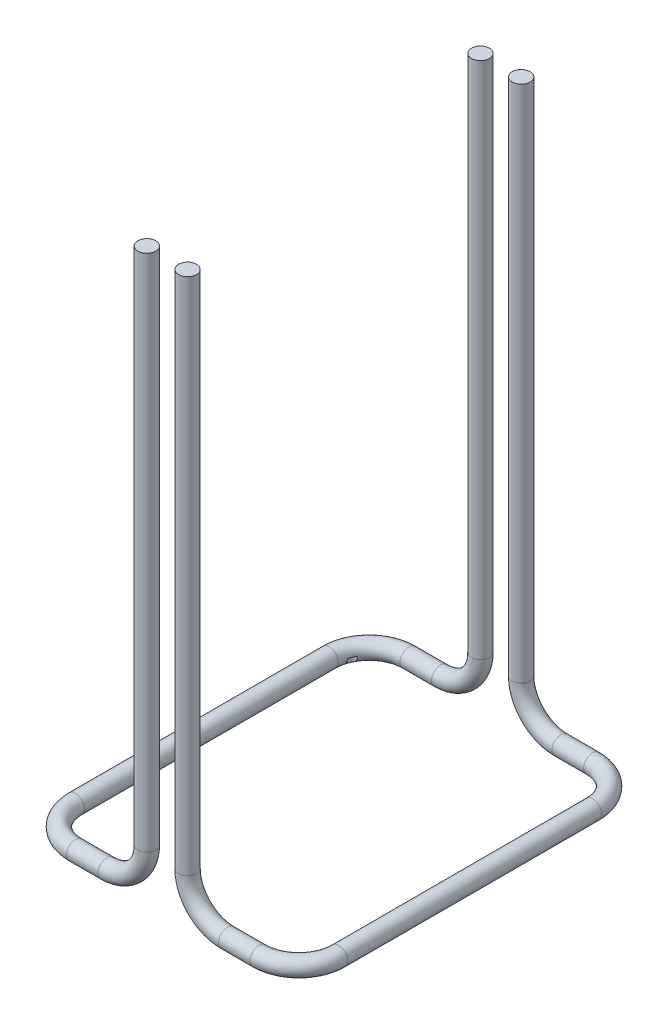
SolidWorks part; units mm, degrees
ref_plane "前视基准面" through (0, 0, 0) normal (0, 0, 1) x (1, 0, 0)
ref_plane "上视基准面" through (0, 0, 0) normal (0, 1, 0) x (1, 0, 0)
ref_plane "右视基准面" through (0, 0, 0) normal (1, 0, 0) x (0, 0, -1)
sketch3d "3D草图1"
  line L0 (0, 0, 0) -> (0, 51.939, 0) construction
  line L1 (25.5, 700.4535, 0) -> (25.5, 50.4535, 0)
  line L2 (75.5, 0.4535, 0) -> (114.9994, 0.4535, 0)
  line L3 (164.9994, 0.4535, -50) -> (164.9994, 0.4535, -368)
  line L4 (114.9994, 0.4535, -418) -> (75.5, 0.4535, -418)
  line L5 (25.5, 50.4535, -418) -> (25.5, 700.4535, -418)
  line L6 (-25.5, 50.4535, -418) -> (-25.5, 700.4535, -418)
  line L7 (-114.9994, 0.4535, -418) -> (-75.5, 0.4535, -418)
  line L8 (-164.9994, 0.4535, -50) -> (-164.9994, 0.4535, -368)
  line L9 (-75.5, 0.4535, 0) -> (-114.9994, 0.4535, 0)
  line L10 (-25.5, 700.4535, 0) -> (-25.5, 50.4535, 0)
  arc A0 (75.5, 0.4535, -418) -> (25.5, 50.4535, -418) centre (75.5, 50.4535, -418) ccw
  arc A1 (164.9994, 0.4535, -368) -> (114.9994, 0.4535, -418) centre (114.9994, 0.4535, -368) ccw
  arc A2 (114.9994, 0.4535, 0) -> (164.9994, 0.4535, -50) centre (114.9994, 0.4535, -50) ccw
  arc A3 (25.5, 50.4535, 0) -> (75.5, 0.4535, 0) centre (75.5, 50.4535, 0) ccw
  arc A4 (-75.5, 0.4535, 0) -> (-25.5, 50.4535, 0) centre (-75.5, 50.4535, 0) cw
  arc A5 (-164.9994, 0.4535, -50) -> (-114.9994, 0.4535, 0) centre (-114.9994, 0.4535, -50) cw
  arc A6 (-114.9994, 0.4535, -418) -> (-164.9994, 0.4535, -368) centre (-114.9994, 0.4535, -368) cw
  arc A7 (-25.5, 50.4535, -418) -> (-75.5, 0.4535, -418) centre (-75.5, 50.4535, -418) cw
  point P11 (25.5, 0.4535, -418)
  point P12 (75.5, 50.4535, -468)
  point P15 (164.9994, 0.4535, -418)
  point P16 (114.9994, 50.4535, -368)
  point P19 (164.9994, 0.4535, 0)
  point P20 (114.9994, 50.4535, -50)
  point P23 (25.5, 0.4535, 0)
  point P24 (75.5, 50.4535, 50)
  point P28 (-75.5, 50.4535, 50)
  point P32 (-114.9994, 50.4535, -50)
  point P36 (-114.9994, 50.4535, -368)
  point P40 (-75.5, 50.4535, -468)
  point P43 (-25.5, 0.4535, 0)
  point P44 (-164.9994, 0.4535, 0)
  point P45 (-164.9994, 0.4535, -418)
  point P46 (-25.5, 0.4535, -418)
  dimension "D5" = 50
  dimension "D6" = 51
  dimension "D1" = 700
  dimension "D2" = 165
  dimension "D4" = 418
sweep "扫描1" add path "3D草图1" circular profile diameter 22.5 parameters "D3"=22.5
sweep "扫描2" add path "3D草图1<4>" circular profile diameter 22.5 parameters "D3"=22.5
sketch3d "3D草图1<4>" same geometry as "3D草图1"
sketch "草图35" plane through (0, 0, 0) normal (0, 1, 0) x (1, 0, 0)
  line L1 (-150, 382.5) -> (150, 382.5)
  line L2 (-150, 382.5) -> (-150, 17.5)
  line L3 (-150, 17.5) -> (150, 17.5)
  line L4 (150, 382.5) -> (150, 17.5)
  line L5 (-150, 382.5) -> (150, 17.5) construction
  line L6 (-150, 17.5) -> (150, 382.5) construction
  circle A0 centre (-150, 382.5) radius 5
  circle A1 centre (150, 382.5) radius 5
  circle A2 centre (150, 17.5) radius 5
  circle A3 centre (-150, 17.5) radius 5
  point P0 (0, 200)
  dimension "D4" = 10
  dimension "D1" = 200
  dimension "D2" = 365
  dimension "D3" = 300
extrude "切除-拉伸1" cut sketch "草图35" against normal through all contours A0 | A3 | A2 | A1
